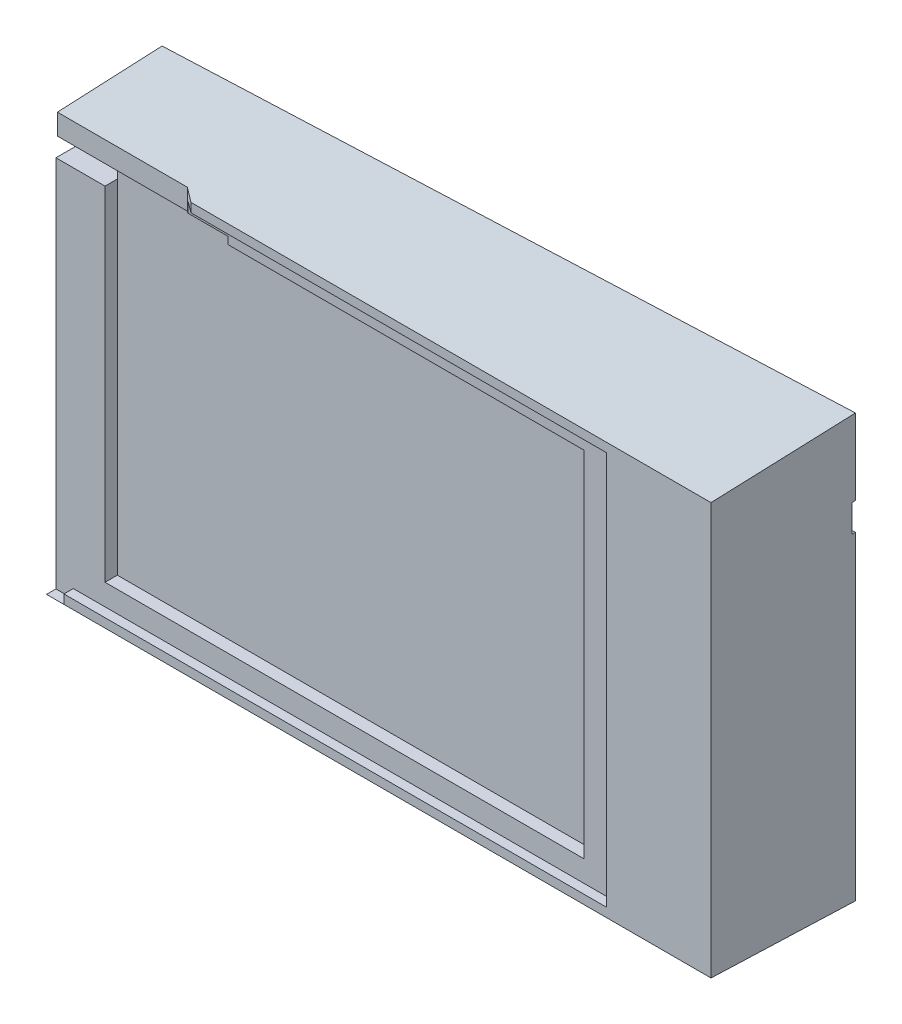
SolidWorks part; units mm, degrees
ref_plane "Front Plane" through (0, 0, 0) normal (0, 0, 1) x (1, 0, 0)
ref_plane "Top Plane" through (0, 0, 0) normal (0, 1, 0) x (1, 0, 0)
ref_plane "Right Plane" through (0, 0, 0) normal (1, 0, 0) x (0, 0, -1)
sketch "Sketch1" plane through (0, 0, 0) normal (0, 0, 1) x (1, 0, 0)
  line L1 (0, 0) -> (92, 0)
  line L2 (0, 0) -> (0, 61)
  line L3 (0, 61) -> (92, 61)
  line L4 (92, 0) -> (92, 61)
  dimension "D1" = 61
  dimension "D2" = 92
ref_plane "Plane1" through (92, 0, 0) normal (1, 0, 0) x (0, 0, -1)
sketch "Sketch2" plane through (92, 0, 0) normal (1, 0, 0) x (0, 0, -1)
  line L1 (0, 61) -> (20, 61.75)
  line L2 (0, 61) -> (0, 4)
  line L3 (0, 4) -> (20, 3.25)
  line L4 (20, 61.75) -> (20, 3.25)
  dimension "D1" = 20
  dimension "D2" = 57
  dimension "D3" = 58.5
ref_plane "Plane2" through (0, 0, 0) normal (1, 0, 0) x (0, 0, -1)
sketch "Sketch3" plane through (0, 0, 0) normal (1, 0, 0) x (0, 0, -1)
  line L1 (0, 61) -> (16, 61.75)
  line L2 (0, 61) -> (0, 4)
  line L3 (0, 4) -> (16, 3.25)
  line L4 (16, 61.75) -> (16, 3.25)
  dimension "D1" = 16
  dimension "D2" = 58.5
  dimension "D3" = 57
ref_plane "Plane3" through (0, 61, 0) normal (0, 1, 0) x (1, 0, 0)
loft "body" add profiles "Sketch3", "Sketch2" connector at (0, 61.75, -16) connector at (92, 61.75, -20)
sketch "Sketch5" plane through (0, 61, 0) normal (0, 1, 0) x (1, 0, 0)
  line L0 (0, 1.5) -> (18, 1.5)
  line L1 (0, -33.55) -> (0, 33.55) construction
  line L2 (18, 1.5) -> (20, 0)
  line L3 (0, 0) -> (92, 0) construction
  line L4 (0, 1.5) -> (0, 0)
  line L5 (0, 0) -> (20, 0)
  dimension "D1" = 1.5
  dimension "D2" = 20
  dimension "D3" = 2
sketch "Sketch6" plane through (0, 0, 0) normal (0, 0, 1) x (1, 0, 0)
  line L0 (23.8, 57.2) -> (23.8, 58.2)
  line L1 (6.8, 8.2) -> (73.1, 8.2)
  line L2 (6.8, 8.2) -> (6.8, 57.2)
  line L3 (6.8, 57.2) -> (73.1, 57.2)
  line L4 (73.1, 8.2) -> (73.1, 57.2)
  line L5 (6.8, 8.2) -> (73.1, 57.2) construction
  line L6 (6.8, 57.2) -> (73.1, 8.2) construction
  line L7 (23.8, 58.2) -> (6.8, 58.2)
  line L9 (0, 61) -> (92, 61) construction
  line L10 (0, 0) -> (0, 61) construction
  line L11 (6.8, 57.2) -> (6.8, 58.2)
  line L12 (6.8, 58.2) -> (6.8, 57.2)
  point P0 (39.95, 32.7)
  dimension "D1" = 66.3
  dimension "D2" = 49
  dimension "D3" = 1
  dimension "D4" = 17
  dimension "D5" = 3.8
  dimension "D6" = 6.8
extrude "film plane" cut sketch "Sketch6" against normal blind 3 contours L11 L3 L0 L7 | L1 L4 L3 L2 region at (15.3, 57.7, 0) region at (39.95, 32.7, 0)
sketch "Sketch7" plane through (0, 0, 0) normal (0, 0, 1) x (1, 0, 0)
  line L0 (0, 0) -> (0, 61) construction
  line L1 (77.5, 59.75) -> (0, 59.75)
  line L2 (77.5, 59.75) -> (77.5, 5.25)
  line L3 (77.5, 5.25) -> (0, 5.25)
  line L4 (0, 59.75) -> (0, 5.25)
  line L5 (92, 0) -> (92, 61) construction
  line L6 (77.5, 5.25) -> (77.5, 4) construction
  line L7 (0, 4) -> (92, 4) construction
  line L8 (77.5, 59.75) -> (77.5, 61) construction
  line L9 (0, 61) -> (92, 61) construction
  line L10 (2.4, 5.25) -> (2.4, 4)
  line L11 (2.4, 4) -> (0, 4)
  line L12 (0, 4) -> (0, 5.25)
  line M5 (0, 4) -> (92, 4)
  dimension "D1" = 54.5
  dimension "D2" = 14.5
  dimension "D3" = 2.4
extrude "Cut-Extrude2" cut sketch "Sketch7" against normal blind 1.3 contours L10 L3 M5 | L3 L2 L1 L4 region at (1.2, 4.625, 0)
sketch "notch" plane through (0, 0, -1.3) normal (0, 0, 1) x (1, 0, 0)
  line L0 (6.8, 58.2) -> (0, 58.2)
  line L1 (0, 59.75) -> (0, 4) construction
  line L2 (0, 58.2) -> (0, 55.7)
  line L3 (0, 55.7) -> (6.8, 55.7)
  line L4 (6.8, 58.2) -> (6.8, 8.2) construction
  line L5 (6.8, 55.7) -> (6.8, 58.2)
  dimension "D1" = 2.5
extrude "notch-cut" cut sketch "notch" against normal blind 4.1
sketch "Sketch10" plane through (-0.6943, 0, -15.9698) normal (-0.0434, 0, -0.9991) x (-0.9991, 0, 0.0434)
  line L0 (-92.7819, 51.25) -> (-86.4841, 51.25)
  line L1 (-92.7819, 3.25) -> (-92.7819, 61.75) construction
  line L2 (-86.4841, 51.25) -> (-86.4841, 47.45)
  line L3 (-86.4841, 47.45) -> (-92.7819, 47.45)
  line L4 (-92.7819, 47.45) -> (-92.7819, 51.25)
  line L6 (-92.7819, 61.75) -> (-0.695, 61.75) construction
  dimension "D1" = 10.5
  dimension "D2" = 3.8
extrude "Cut-Extrude4" cut sketch "Sketch10" against normal blind 0.5
sketch "Sketch11" plane through (-0.6943, 0, -15.9698) normal (-0.0434, 0, -0.9991) x (-0.9991, 0, 0.0434)
  line L0 (-92.7819, 3.25) -> (-92.7819, 47.45) construction
  line L1 (-72.5, 14.5) -> (-64, 14.5)
  line L2 (-75, 17) -> (-75, 48)
  line L3 (-72.5, 50.5) -> (-64, 50.5)
  line L4 (-61.5, 17) -> (-61.5, 48)
  line L5 (-24.5, 14.5) -> (-16, 14.5)
  line L6 (-27, 17) -> (-27, 48)
  line L7 (-24.5, 50.5) -> (-16, 50.5)
  line L8 (-13.5, 17) -> (-13.5, 48)
  line L11 (-0.695, 32.5) -> (-92.7819, 32.5) construction
  line L12 (-0.695, 3.25) -> (-0.695, 61.75) construction
  line L13 (0, 0) -> (0, 61) construction
  arc A0 (-24.5, 14.5) -> (-27, 17) centre (-24.5, 17) cw
  arc A1 (-16, 14.5) -> (-13.5, 17) centre (-16, 17) ccw
  arc A2 (-16, 50.5) -> (-13.5, 48) centre (-16, 48) cw
  arc A3 (-27, 48) -> (-24.5, 50.5) centre (-24.5, 48) cw
  arc A4 (-75, 48) -> (-72.5, 50.5) centre (-72.5, 48) cw
  arc A5 (-64, 50.5) -> (-61.5, 48) centre (-64, 48) cw
  arc A6 (-64, 14.5) -> (-61.5, 17) centre (-64, 17) ccw
  arc A7 (-72.5, 14.5) -> (-75, 17) centre (-72.5, 17) cw
  point P10 (-13.5, 32.5)
  point P27 (-75, 50.5)
  point P34 (-75, 14.5)
  dimension "D6" = 2.5
  dimension "D1" = 36
  dimension "D3" = 34.5
  dimension "D4" = 13.5
  dimension "D2" = 13.5
  dimension "D5" = 13.5
extrude "Cut-Extrude5" cut sketch "Sketch11" against normal blind 1.5
extrude "Cut-Extrude6" cut sketch "Sketch5" against normal blind 5 and the other way through all
equation "\"D5@Sketch11\"=\"D2@Sketch11\""
